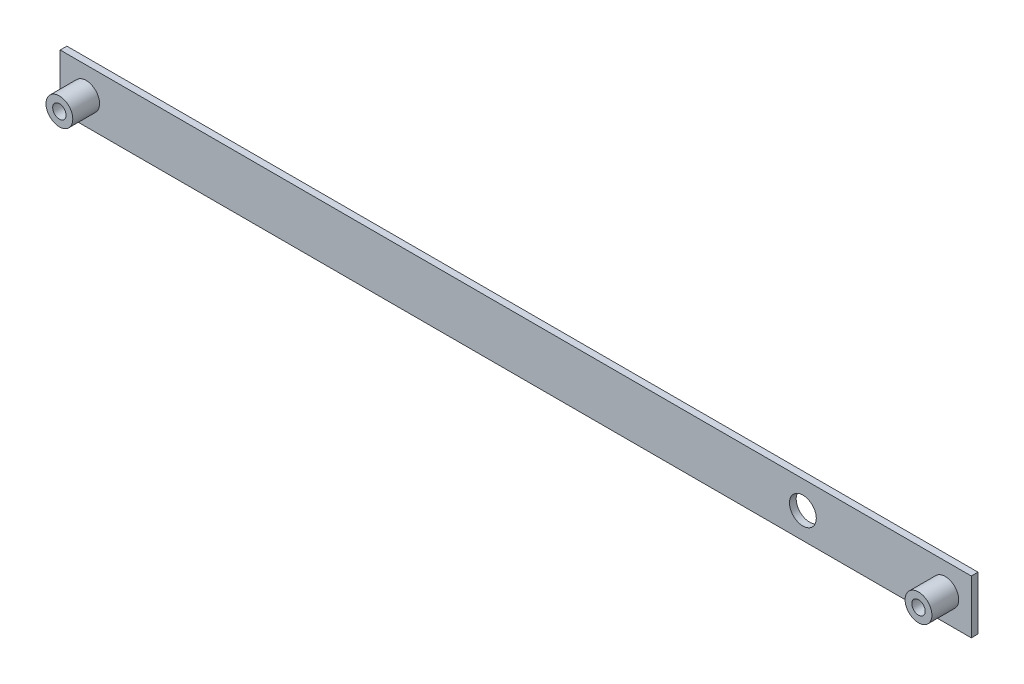
SolidWorks part; units mm, degrees
ref_plane "Front" through (0, 0, 0) normal (0, 0, 1) x (1, 0, 0)
ref_plane "Top" through (0, 0, 0) normal (0, 1, 0) x (1, 0, 0)
ref_plane "Right" through (0, 0, 0) normal (1, 0, 0) x (0, 0, -1)
sketch "Sketch1" plane through (0, 0, 0) normal (0, 0, 1) x (1, 0, 0)
  line L0 (0, 0) -> (407.162, 0) construction
  line L2 (-12.319, 12.7) -> (419.481, 12.7)
  line L3 (-12.319, 12.7) -> (-12.319, -12.7)
  line L4 (-12.319, -12.7) -> (419.481, -12.7)
  line L5 (419.481, 12.7) -> (419.481, -12.7)
  line L6 (-12.319, 12.7) -> (419.481, -12.7) construction
  line L7 (-12.319, -12.7) -> (419.481, 12.7) construction
  circle A0 centre (0, 0) radius 3.175
  circle A1 centre (407.162, 0) radius 3.175
  point P5 (203.581, 0)
  dimension "D1" = 6.35
  dimension "D2" = 6.35
  dimension "D3" = 431.8
  dimension "D4" = 25.4
extrude "Boss-Extrude1" add sketch "Sketch1" along normal blind 3.175
sketch "Sketch2" plane through (0, 0, 3.175) normal (0, 0, 1) x (1, 0, 0)
  circle A0 centre (0, 0) radius 3.175 construction
  circle A1 centre (0, 0) radius 3.175
  circle A2 centre (0, 0) radius 6.35
  circle A3 centre (407.162, 0) radius 3.175 construction
  circle A4 centre (407.162, 0) radius 3.175
  circle A5 centre (407.162, 0) radius 6.35
  dimension "D1" = 12.7
  dimension "D2" = 12.7
extrude "Boss-Extrude2" add sketch "Sketch2" along normal blind 12.7
sketch "Sketch3" plane through (0, 0, 3.175) normal (0, 0, 1) x (1, 0, 0)
  circle A1 centre (339.6683, -0.34) radius 6.35
extrude "Cut-Extrude1" cut sketch "Sketch3" against normal up to next
